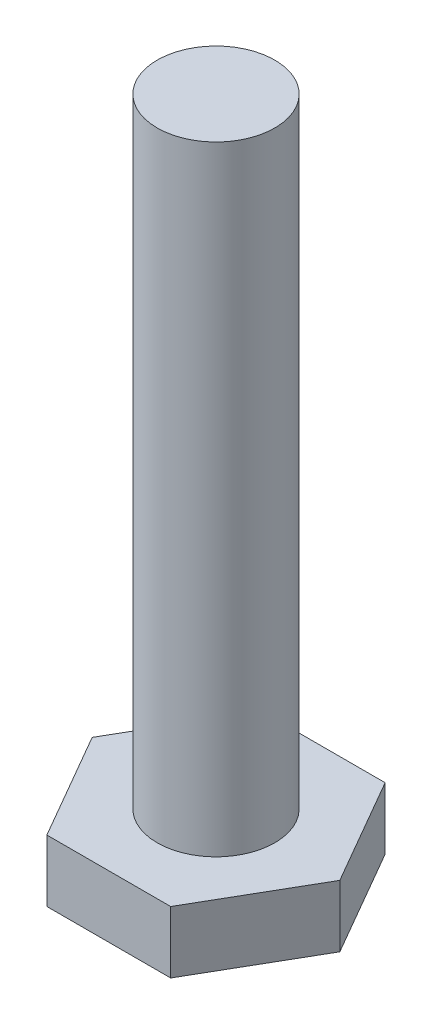
SolidWorks part; units mm, degrees
material "201 Annealed Stainless Steel (SS)"
ref_plane "Front Plane" through (0, 0, 0) normal (0, 0, 1) x (1, 0, 0)
ref_plane "Top Plane" through (0, 0, 0) normal (0, 1, 0) x (1, 0, 0)
ref_plane "Right Plane" through (0, 0, 0) normal (1, 0, 0) x (0, 0, -1)
sketch "Sketch1" plane through (0, 0, 0) normal (0, 1, 0) x (1, 0, 0)
  line L1 (10, 0) -> (5, 8.6603)
  line L2 (5, 8.6603) -> (-5, 8.6603)
  line L3 (-5, 8.6603) -> (-10, 0)
  line L4 (-10, 0) -> (-5, -8.6603)
  line L5 (-5, -8.6603) -> (5, -8.6603)
  line L6 (5, -8.6603) -> (10, 0)
  circle A0 centre (0, 0) radius 8.6603 construction
  circle A1 centre (0, 0) radius 4.75
  dimension "D1" = 9.5
  dimension "D2" = 10
extrude "Boss-Extrude1" add sketch "Sketch1" along normal blind 5
extrude "Boss-Extrude2" add sketch "Sketch1<2>" along normal blind 55 contours A1 region at (0, 0, 0)
sketch "Sketch1<2>" plane through (0, 0, 0) normal (0, 1, 0) x (1, 0, 0) same geometry as "Sketch1"
